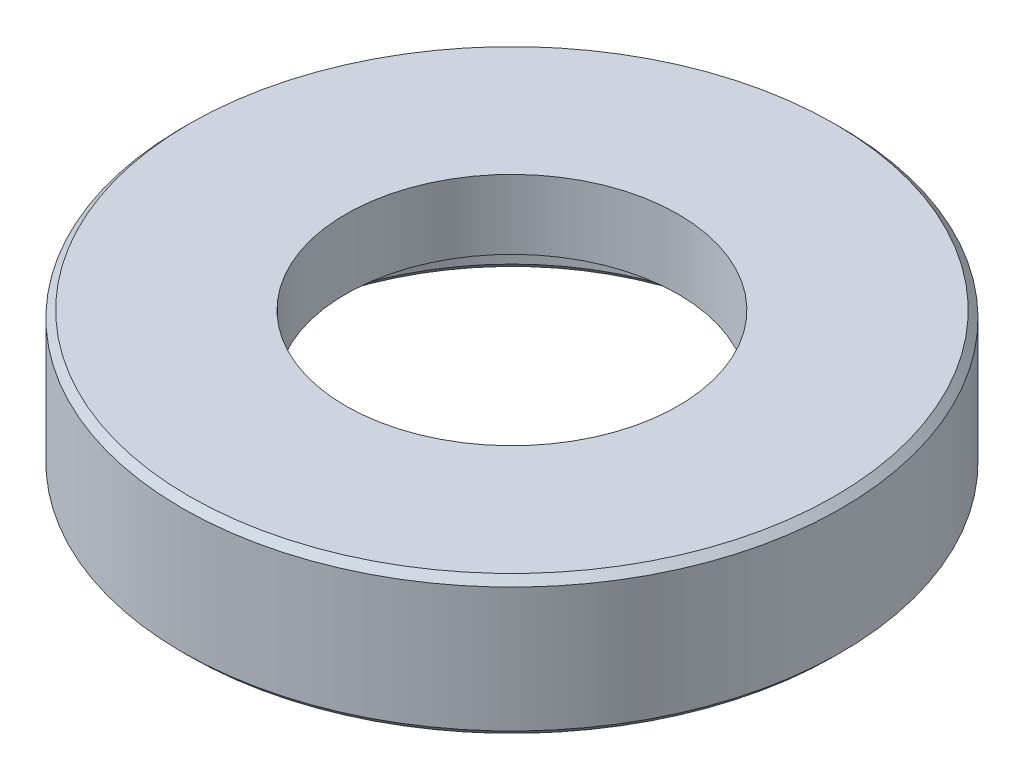
SolidWorks part; units mm, degrees
material "AISI 1045 Steel, cold drawn"
ref_plane "Front Plane" through (0, 0, 0) normal (0, 0, 1) x (1, 0, 0)
ref_plane "Top Plane" through (0, 0, 0) normal (0, 1, 0) x (1, 0, 0)
ref_plane "Right Plane" through (0, 0, 0) normal (1, 0, 0) x (0, 0, -1)
sketch "Sketch1" plane through (0, 0, 0) normal (0, 1, 0) x (1, 0, 0)
  circle A0 centre (0, 0) radius 6
  circle A1 centre (0, 0) radius 8.75
  circle A2 centre (0, 0) radius 11.9
extrude "Boss-Extrude1" add sketch "Sketch1" along normal blind 5 contours A2
extrude "Cut-Extrude1" cut sketch "Sketch1<3>" along normal up to surface (5 mm away) contours A0 region at (0, 0, 0) up to face at (0, 5, 11.9)
sketch "Sketch1<3>" plane through (0, 0, 0) normal (0, 1, 0) x (1, 0, 0) same geometry as "Sketch1"
extrude "Cut-Extrude2" cut sketch "Sketch1<4>" along normal blind 2.5 contours A1 A0 region at (-8.5025, 0, 0)
sketch "Sketch1<4>" plane through (0, 0, 0) normal (0, 1, 0) x (1, 0, 0) same geometry as "Sketch1"
chamfer "Chamfer1" distance 0.25 angle 45 3 edges at (0, 0, 8.75) (0, 0, 11.9) (0, 5, 11.9)
